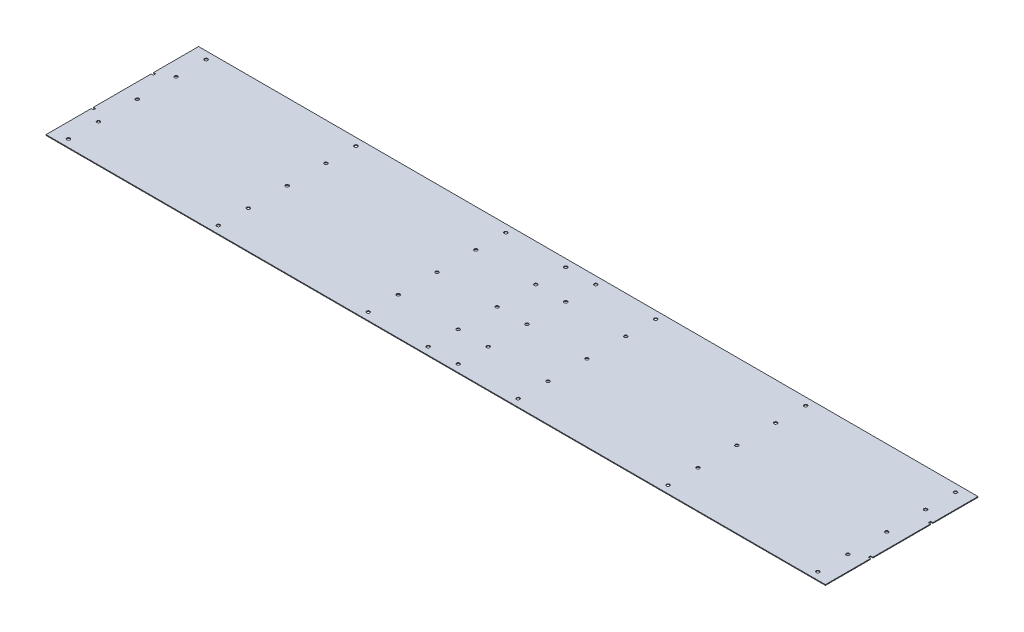
SolidWorks part; units mm, degrees
ref_plane "Front Plane" through (0, 0, 0) normal (0, 0, 1) x (1, 0, 0)
ref_plane "Top Plane" through (0, 0, 0) normal (0, 1, 0) x (1, 0, 0)
ref_plane "Right Plane" through (0, 0, 0) normal (1, 0, 0) x (0, 0, -1)
sketch "Sketch1" plane through (0, 0, 0) normal (0, 1, 0) x (1, 0, 0)
  line L0 (-20, -41.5) -> (-20, -101.8)
  line L1 (-20, -101.8) -> (1020, -101.8)
  line L2 (1020, -101.8) -> (1020, -41.5)
  line L3 (1020, -41.5) -> (-20, -41.5) construction
  line L4 (0, 0) -> (-17, 0) construction
  line L5 (-20, -41.5) -> (-17, -41.5)
  line L7 (-17, 41.5) -> (-20, 41.5)
  line L8 (-20, 41.5) -> (-20, 101.8)
  line L9 (-20, 101.8) -> (1020, 101.8)
  line L10 (1020, 101.8) -> (1020, 41.5)
  line L11 (1020, 41.5) -> (1017, 41.5)
  line L13 (1017, -41.5) -> (1020, -41.5)
  line L14 (0, 51.8) -> (480, 51.8) construction
  line L15 (-17, 41.5) -> (-17, 38.5)
  line L16 (-17, 41.5) -> (1017, 41.5) construction
  line L17 (1017, 41.5) -> (1017, -41.5) construction
  line L18 (-17, 41.5) -> (-17, -41.5) construction
  line L19 (-17, 38.5) -> (-20, 38.5)
  line L20 (-20, 38.5) -> (-20, -38.5)
  line L21 (-20, -38.5) -> (-17, -38.5)
  line L22 (-17, -38.5) -> (-17, -41.5)
  line L23 (1017, 41.5) -> (1017, 38.5)
  line L24 (1017, 38.5) -> (1020, 38.5)
  line L25 (1020, 38.5) -> (1020, -38.5)
  line L26 (1020, -38.5) -> (1017, -38.5)
  line L27 (1017, -38.5) -> (1017, -41.5)
  line L28 (1020, 0) -> (1017, 0) construction
  line L29 (480, 51.8) -> (480, -51.8) construction
  line L30 (-17, 0) -> (-20, 0) construction
  line L31 (0, 51.8) -> (0, -51.8) construction
  line L32 (480, -51.8) -> (0, -51.8) construction
  line L33 (0, 51.8) -> (0, 91.8) construction
  line L34 (0, 91.8) -> (480, 91.8) construction
  line L35 (480, 91.8) -> (480, 51.8) construction
  line L36 (480, -51.8) -> (480, -91.8) construction
  line L37 (480, -91.8) -> (0, -91.8) construction
  line L38 (0, -91.8) -> (0, -51.8) construction
  line L39 (0, 0) -> (480, 0) construction
  line L40 (200, 91.8) -> (200, 51.8) construction
  line L41 (200, 51.8) -> (200, 0) construction
  line L42 (200, 0) -> (200, -51.8) construction
  line L43 (200, -51.8) -> (200, -91.8) construction
  line L44 (500, 101.8) -> (500, -101.8) construction
  line L45 (480, 91.8) -> (500, 91.8) construction
  line L46 (500, 91.8) -> (520, 91.8) construction
  line L47 (520, 91.8) -> (520, -91.8) construction
  line L48 (520, -91.8) -> (480, -91.8) construction
  line L49 (480, -51.8) -> (520, -51.8) construction
  line L50 (400, 91.8) -> (400, -91.8) construction
  line L51 (480, 0) -> (520, 0) construction
  line L53 (480, 51.8) -> (520, 51.8) construction
  line L54 (600, 91.8) -> (600, -91.8) construction
  line L56 (800, 91.8) -> (800, -91.8) construction
  line L58 (1000, 91.8) -> (1000, -91.8) construction
  circle A0 centre (0, -51.8) radius 2.15
  circle A30 centre (0, 51.8) radius 2.15
  circle A31 centre (0, -91.8) radius 2.15
  circle A32 centre (0, 91.8) radius 2.15
  circle A33 centre (200, -91.8) radius 2.15
  circle A34 centre (200, -51.8) radius 2.15
  circle A35 centre (200, 51.8) radius 2.15
  circle A36 centre (200, 91.8) radius 2.15
  circle A53 centre (0, 0) radius 2.15
  circle A54 centre (480, 0) radius 2.15
  circle A55 centre (200, 0) radius 2.15
  circle A59 centre (480, 91.8) radius 2.15
  circle A60 centre (480, 51.8) radius 2.15
  circle A61 centre (480, -51.8) radius 2.15
  circle A62 centre (480, -91.8) radius 2.15
  circle A63 centre (400, -91.8) radius 2.15
  circle A64 centre (400, -51.8) radius 2.15
  circle A65 centre (400, 51.8) radius 2.15
  circle A66 centre (400, 91.8) radius 2.15
  circle A67 centre (600, -91.8) radius 2.15
  circle A68 centre (600, -51.8) radius 2.15
  circle A69 centre (600, 51.8) radius 2.15
  circle A70 centre (600, 91.8) radius 2.15
  circle A71 centre (800, -91.8) radius 2.15
  circle A72 centre (800, -51.8) radius 2.15
  circle A73 centre (800, 51.8) radius 2.15
  circle A74 centre (800, 91.8) radius 2.15
  circle A75 centre (1000, -91.8) radius 2.15
  circle A76 centre (1000, -51.8) radius 2.15
  circle A77 centre (1000, 51.8) radius 2.15
  circle A78 centre (1000, 91.8) radius 2.15
  circle A79 centre (520, -91.8) radius 2.15
  circle A80 centre (520, -51.8) radius 2.15
  circle A81 centre (520, 0) radius 2.15
  circle A82 centre (520, 51.8) radius 2.15
  circle A83 centre (520, 91.8) radius 2.15
  circle A84 centre (600, 0) radius 2.15
  circle A85 centre (800, 0) radius 2.15
  circle A86 centre (1000, 0) radius 2.15
  circle A87 centre (400, 0) radius 2.15
  point P2 (-18.5, 38.5)
  point P17 (0, 71.8)
  dimension "D12" = 4.3
  dimension "D8" = 3
  dimension "D1" = 3
  dimension "D6" = 40
  dimension "D7" = 10
  dimension "D4" = 20
  dimension "D15" = 200
  dimension "D3" = 13.3
  dimension "D11" = 13.3
  dimension "D2" = 77
  dimension "D5" = 20
  dimension "D10" = 40
  dimension "D9" = 6
  dimension "D14" = 2
extrude "Boss-Extrude1" add sketch "Sketch1" along normal blind 1 contours L27 L26 L25 L24 L23 L11 L10 L9 L8 L7 L15 L19 L20 L21 L22 L5 L0 L1 L2 L13 A54 A53 A36 A35 A34 A33 A32 A31 A30 A0 region at (500, 0, 0)
equation "\"skin_sheetmetal_thickness\"= 0.80"
equation "\"base_width_skin_spacer\" = \"base_width_skin_target_width\" - 4 * \"skin_sheetmetal_thickness\" - 2 * \"base_width_skin_target_bend_radius\""
equation "\"base_width_skin_inner\" = \"base_width_skin_spacer\" + 2 * \"skin_sheetmetal_thickness\""
equation "\"base_width_skin_outer\" = \"base_width_skin_inner\" + 2 * \"skin_sheetmetal_thickness\""
equation "\"bend_cut_width\"= 3"
equation "\"bend_cut_length\"= 3"
equation "\"bend_offset_inner\"= 12.5"
equation "\"bend_offset_outer\" = \"bend_offset_inner\" + \"skin_sheetmetal_thickness\""
equation "\"border_offset_ends\"= 20"
equation "\"border_offset_sides\"= 10"
equation "\"border_offset_flange_horiz\"= 10"
equation "\"rivet_size\"= 4.3"
equation "\"rivet_offset_ends\"= \"rivet_spacing_horiz\"/2 - \"border_offset_ends\""
equation "\"rivet_spacing_horiz\"= 200"
equation "\"rivet_spacing_vert\"= 40"
equation "\"rivet_spacing_offset_right\"= 40"
equation "\"base_length\"= 200"
equation "\"base_width_skin_spacer_length\" = 430"
equation "\"bend_offset_spacer_tab\"= 21.0"
equation "\"D6@Sketch1\"=\"rivet_spacing_vert\""
equation "\"D3@Sketch1\"=\"bend_offset_outer\""
equation "\"D1@Sketch1\"=\"bend_cut_length\""
equation "\"D8@Sketch1\"=\"bend_cut_width\""
equation "\"D2@Sketch1\"=\"base_width_skin_outer\""
equation "\"D4@Sketch1\"=\"border_offset_ends\""
equation "\"D7@Sketch1\"=\"border_offset_flange_horiz\""
equation "\"D12@Sketch1\"=\"rivet_size\""
equation "\"D15@Sketch1\"=\"rivet_spacing_horiz\""
equation "\"D5@Sketch1\"=\"border_offset_ends\""
equation "\"D10@Sketch1\"=\"rivet_spacing_offset_right\""
equation "\"base_width_skin_target_width\" = 80"
equation "\"base_width_skin_target_bend_radius\" = 1.5"
